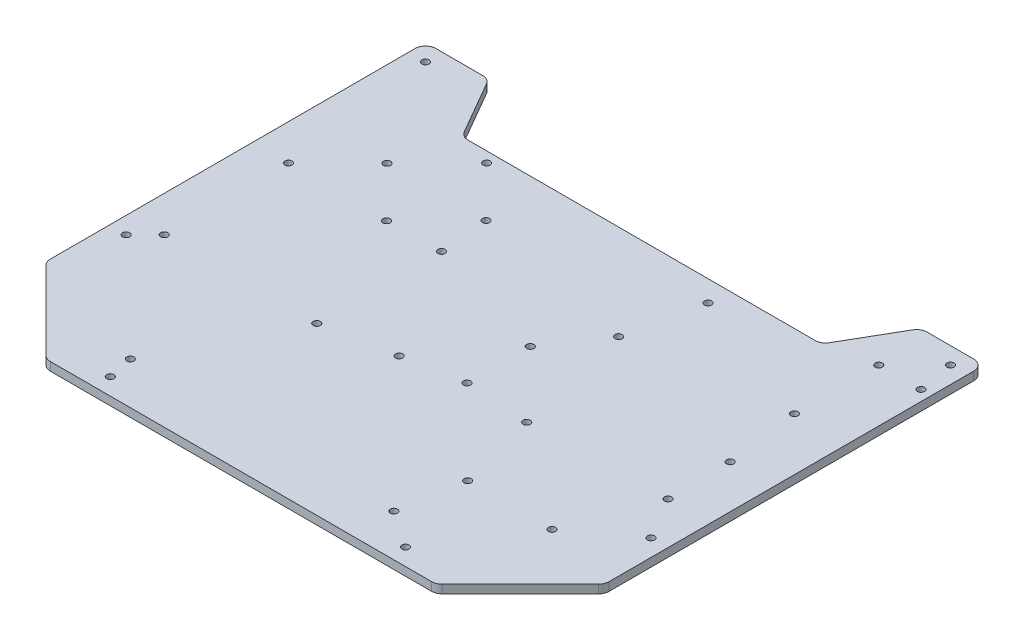
SolidWorks part; units mm, degrees
material "Acier non allié"
ref_plane "Front" through (0, 0, 0) normal (0, 0, 1) x (1, 0, 0)
ref_plane "Top" through (0, 0, 0) normal (0, 1, 0) x (1, 0, 0)
ref_plane "Right" through (0, 0, 0) normal (1, 0, 0) x (0, 0, -1)
sketch "Main scetch" plane through (0, 0, 0) normal (0, 1, 0) x (1, 0, 0)
  line L1 (0, 0) -> (132.5, 0) construction
  line L2 (0, 0) -> (0, 220) construction
  line L3 (0, 220) -> (132.5, 220) construction
  line L4 (132.5, 0) -> (132.5, 220) construction
  line L13 (-92.5, 0) -> (92.5, 0)
  line L14 (92.5, 0) -> (132.5, 40)
  line L15 (132.5, 40) -> (132.5, 220)
  line L16 (132.5, 220) -> (102.5, 220)
  line L17 (102.5, 220) -> (85.1795, 190)
  line L18 (85.1795, 190) -> (-85.1795, 190)
  line L19 (-102.5, 220) -> (-85.1795, 190)
  line L20 (-132.5, 220) -> (-102.5, 220)
  line L21 (-132.5, 40) -> (-132.5, 220)
  line L22 (-92.5, 0) -> (-132.5, 40)
  point P11 (0, 190)
  dimension "132.5" = 132.5
  dimension "D2" = 220
  dimension "D1" = 40
  dimension "D3" = 40
  dimension "D4" = 30
  dimension "D5" = 60
  dimension "D6" = 30
extrude "Main extrusion" add sketch "Main scetch" along normal blind 4
fillet "Congé1" radius 5 10 edges at (-132.5, 2, -40) (-92.5, 2, 0) (92.5, 2, 0) (132.5, 2, -40) (132.5, 2, -220) (102.5, 2, -220) (85.1795, 2, -190) (-85.1795, 2, -190) (-102.5, 2, -220) (-132.5, 2, -220)
sketch "Esquisse1" plane through (0, 4, 0) normal (0, 1, 0) x (1, 0, 0)
  line L0 (0, 0) -> (0, 218.5516) construction
  line L1 (132.5, 42.0711) -> (132.5, 215) construction
  line L2 (127.5, 220) -> (105.3868, 220) construction
  line L3 (-90.4289, 0) -> (90.4289, 0) construction
  circle A0 centre (70, 8) radius 1
  circle A1 centre (124.5, 70) radius 1
  circle A2 centre (124.5, 212) radius 1
  circle A3 centre (-124.5, 212) radius 1
  circle A4 centre (-124.5, 70) radius 1
  circle A5 centre (-70, 8) radius 1
  dimension "D1" = 2
  dimension "D2" = 2
  dimension "D3" = 2
  dimension "D4" = 8
  dimension "D5" = 8
  dimension "D6" = 8
  dimension "D7" = 8
  dimension "D8" = 70
  dimension "D9" = 70
extrude "Enlèv. mat.-Extru.1" cut sketch "Esquisse1" against normal through all
hole_wizard "Dégagement M31" positions "Esquisse2" profile "Esquisse3" hole size "M3" standard "ISO" end condition through all
sketch "Esquisse2" plane through (0, 4, 0) normal (0, 1, 0) x (1, 0, 0)
  point P0 (-124.5, 212)
  point P3 (-124.5, 70)
  point P6 (-70, 8)
  point P9 (70, 8)
  point P12 (124.5, 70)
  point P15 (124.5, 212)
sketch "Esquisse3" plane through (-124.5, 4, -212) normal (1, 0, 0) x (0, 0, 1)
  line L0 (0, 0) -> (0, 4)
  line L1 (0, 4) -> (1.7, 4)
  line L2 (1.7, 4) -> (1.7, 0)
  line L5 (1.7, 0) -> (0, 0)
  line L11 (0, -6.35) -> (0, 107.95) construction
  dimension "Diamètre du perçage jusqu'au prochain" = 3.4
  dimension "Profondeur du perçage jusqu'au prochain" = 4
sketch "Esquisse4" plane through (0, 4, 0) normal (0, 1, 0) x (1, 0, 0)
  line L0 (-132.5, 215) -> (-132.5, 42.0711) construction
  line L2 (82.2927, 190) -> (-82.2927, 190) construction
  line L3 (132.5, 42.0711) -> (132.5, 215) construction
  line L4 (-90.4289, 0) -> (90.4289, 0) construction
  line L5 (127.5, 220) -> (105.3868, 220) construction
  circle A1 centre (-68.5, 185) radius 1
  circle A5 centre (41.5, 180) radius 1
  circle A6 centre (34.12, 145) radius 1
  circle A7 centre (107.5, 155) radius 1
  circle A8 centre (127.5, 195) radius 1
  circle A9 centre (112, 120) radius 1
  circle A10 centre (112.5, 90) radius 1
  circle A11 centre (17.2, 120) radius 1
  circle A12 centre (17.2, 90) radius 1
  circle A13 centre (47.5, 88) radius 1
  circle A14 centre (57.5, 50) radius 1
  circle A15 centre (97.5, 50) radius 1
  circle A16 centre (52.5, 20) radius 1
  circle A17 centre (-10, 85) radius 1
  circle A18 centre (-72.5, 20) radius 1
  circle A19 centre (107.5, 195) radius 1
  circle A20 centre (-68.5, 137.5) radius 1
  circle A21 centre (-92, 161.25) radius 1
  circle A22 centre (-45, 161.25) radius 1
  circle A23 centre (-115.5, 138) radius 1
  circle A24 centre (-42.86, 138) radius 1
  circle A25 centre (-115.5, 79.07) radius 1
  circle A26 centre (-42.8904, 78.82) radius 1
  point P14 (-49.1389, 55.7421)
  point P15 (-47.5736, 66.5654)
  point P58 (-101.5413, 56.7612)
  point P59 (-47.8166, 56.7612)
  dimension "D4" = 2
  dimension "D13" = 2
  dimension "D16" = 2
  dimension "D19" = 2
  dimension "D24" = 2
  dimension "D25" = 2
  dimension "D28" = 2
  dimension "D30" = 2
  dimension "D32" = 2
  dimension "D36" = 2
  dimension "D37" = 2
  dimension "D40" = 2
  dimension "D48" = 2
  dimension "D49" = 2
  dimension "D50" = 2
  dimension "D52" = 2
  dimension "D57" = 2
  dimension "D63" = 2
  dimension "D64" = 2
  dimension "D11" = 2
  dimension "D12" = 2
  dimension "D65" = 2
  dimension "D66" = 2
  dimension "D14" = 174
  dimension "D15" = 10
  dimension "D17" = 166.62
  dimension "D18" = 45
  dimension "D20" = 25
  dimension "D21" = 65
  dimension "D22" = 5
  dimension "D23" = 25
  dimension "D26" = 20.5
  dimension "D27" = 100
  dimension "D29" = 30
  dimension "D31" = 115.3
  dimension "D33" = 115.3
  dimension "D34" = 132
  dimension "D35" = 85
  dimension "D38" = 50
  dimension "D39" = 75
  dimension "D41" = 35
  dimension "D42" = 80
  dimension "D43" = 20
  dimension "D44" = 20
  dimension "D45" = 205
  dimension "D46" = 85
  dimension "D47" = 142.5
  dimension "D51" = 25
  dimension "D53" = 25
  dimension "D54" = 5
  dimension "D55" = 64
  dimension "D56" = 47.5
  dimension "D58" = 64
  dimension "D59" = 28.75
  dimension "D60" = 40.5
  dimension "D61" = 47
  dimension "D62" = 28.75
  dimension "D7" = 59.18
  dimension "D8" = 72.64
  dimension "D9" = 58.93
  dimension "D10" = 72.61
  dimension "D67" = 17
  dimension "D68" = 138
extrude "Enlèv. mat.-Extru.2" cut sketch "Esquisse4" against normal through all
hole_wizard "Dégagement M32" positions "Esquisse5" profile "Esquisse6" hole size "M3" standard "ISO" end condition through all
sketch "Esquisse5" plane through (0, 4, 0) normal (0, 1, 0) x (1, 0, 0)
  point P0 (-68.5, 185)
  point P9 (17.2, 120)
  point P18 (34.12, 145)
  point P21 (41.5, 180)
  point P24 (107.5, 155)
  point P27 (127.5, 195)
  point P30 (112, 120)
  point P33 (112.5, 90)
  point P36 (47.5, 88)
  point P39 (17.2, 90)
  point P42 (57.5, 50)
  point P45 (97.5, 50)
  point P48 (-10, 85)
  point P51 (-72.5, 20)
  point P54 (52.5, 20)
  point P57 (107.5, 195)
  point P72 (-68.5, 137.5)
  point P76 (-92, 161.25)
  point P79 (-45, 161.25)
  point P86 (-115.5, 138)
  point P89 (-42.86, 138)
  point P92 (-115.5, 79.07)
  point P95 (-42.8904, 78.82)
sketch "Esquisse6" plane through (-68.5, 4, -185) normal (1, 0, 0) x (0, 0, 1)
  line L0 (0, 0) -> (0, 4)
  line L1 (0, 4) -> (1.7, 4)
  line L2 (1.7, 4) -> (1.7, 0)
  line L5 (1.7, 0) -> (0, 0)
  line L11 (0, -6.35) -> (0, 107.95) construction
  dimension "Diamètre du perçage jusqu'au prochain" = 3.4
  dimension "Profondeur du perçage jusqu'au prochain" = 4
equation "\"WIDTH\"= 300mm'Total width of the robot"
equation "\"LENGTH\"= 220mm'Total length of the robot"
equation "\"D2@Main scetch\" = \"LENGTH\""
equation "\"CUT_DEPTH\"= 45mm'Depth of the cut on the edges of the plate"
equation "\"Plate_th\"= 3mm'Thickness of the plate"
equation "\"D1\"= \"Plate_th\""
equation "\"D47@Esquisse4\"=(80+205)/2"
